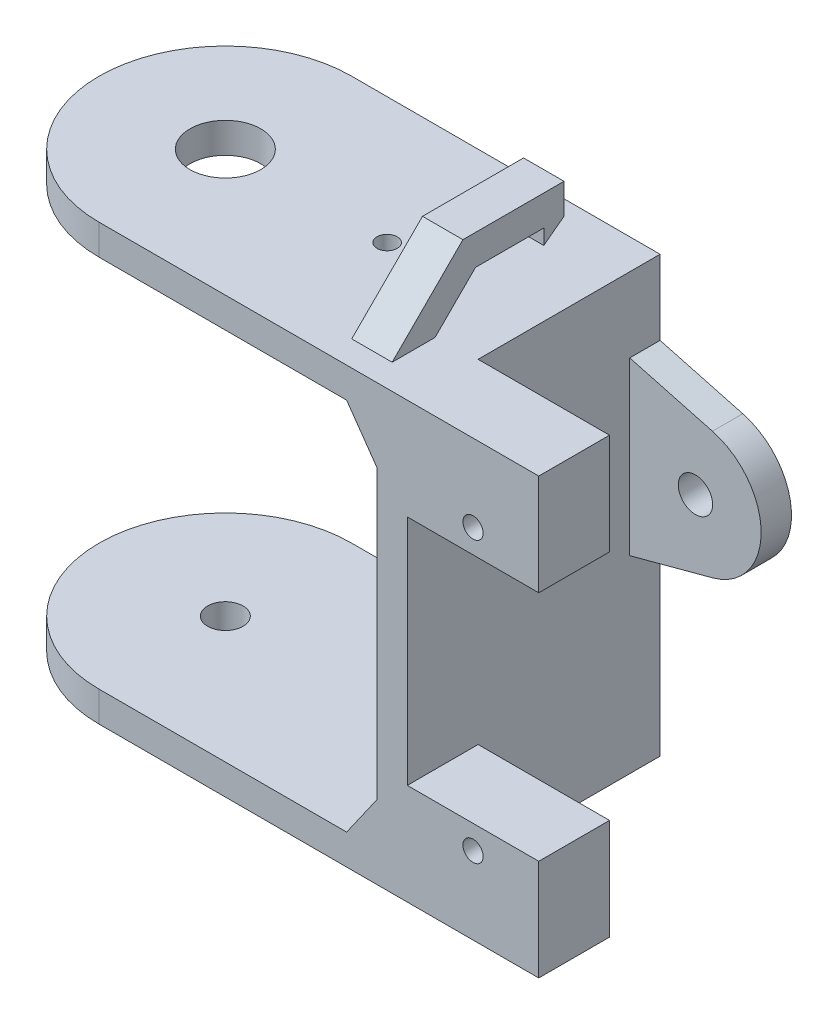
SolidWorks part; units mm, degrees
ref_plane "Plano frontal" through (0, 0, 0) normal (0, 0, 1) x (1, 0, 0)
ref_plane "Plano superior" through (0, 0, 0) normal (0, 1, 0) x (1, 0, 0)
ref_plane "Plano direito" through (0, 0, 0) normal (1, 0, 0) x (0, 0, -1)
sketch "Esboço1" plane through (0, 0, 0) normal (0, 0, 1) x (1, 0, 0)
  line L1 (0, -21.5) -> (-43, -21.5)
  line L2 (-43, -21.5) -> (-43, -18.5)
  line L3 (-43, -18.5) -> (-3, -18.5)
  line L4 (-3, -18.5) -> (-3, 18.5)
  line L5 (-3, 18.5) -> (-43, 18.5)
  line L6 (-43, 18.5) -> (-43, 21.5)
  line L7 (-43, 21.5) -> (0, 21.5)
  line L8 (0, 21.5) -> (13, 21.5)
  line L9 (13, 21.5) -> (13, 11.5)
  line L10 (13, 11.5) -> (0, 11.5)
  line L11 (0, -21.5) -> (13, -21.5)
  line L12 (13, -21.5) -> (13, -11.5)
  line L13 (13, -11.5) -> (0, -11.5)
  line L14 (0, 11.5) -> (0, -11.5)
  line L17 (0, 0) -> (31.9596, 0) construction
  circle A0 centre (6.5, 13.85) radius 1
  circle A2 centre (6.5, -13.85) radius 1
  point P4 (0, 0)
  point P7 (0, 0)
  point P12 (-7, 23)
  point P16 (0, 0)
  point P19 (0, 0)
  point P20 (-3, 0)
  point P23 (6.5, 11.5)
  point P24 (0, 0)
  point P30 (6.5, -24.315)
  point P31 (0, 21.5)
  point P32 (0, 21.5)
  point P33 (0, -21.5)
  dimension "D9" = 2
  dimension "D1" = 23
  dimension "D2" = 3
  dimension "D3" = 13
  dimension "D5" = 3
  dimension "D6" = 37
  dimension "D7" = 40
  dimension "D10" = 27.7
extrude "Ressalto-extrusão1" add sketch "Esboço1" along normal mid plane 25
sketch "Esboço2" plane through (0, 21.5, 0) normal (0, 1, 0) x (1, 0, 0)
  line L0 (-30.5, 12.5) -> (-64.1593, 12.5)
  line L1 (-64.1593, 12.5) -> (-64.1593, -12.5)
  line L2 (0, 0) -> (-3.8141, 0) construction
  line L3 (-64.1593, -12.5) -> (-30.5, -12.5)
  line L4 (-43, -12.5) -> (-43, 12.5) construction
  line L5 (13, 12.5) -> (-43, 12.5) construction
  circle A0 centre (-30.5, 0) radius 3.5
  circle A1 centre (-14.5, 0) radius 1
  arc A7 (-30.5, 12.5) -> (-30.5, -12.5) centre (-30.5, 0) ccw
  point P4 (-21.75, 0)
  point P5 (-59.3343, 15.2284)
  point P9 (-3.8141, 0)
  point P10 (-10.9, 0)
  point P13 (0, 0)
  point P19 (-35, 0)
  point P25 (-57.8021, 17.5)
  point P26 (-64.9885, 25.6125)
  point P27 (-73.7699, 34.1272)
  point P28 (-63.3875, 22.5081)
  point P29 (-64.9885, 24.6125)
  line M3 (13, 12.5) -> (-43, 12.5)
  line M4 (-43, 12.5) -> (-43, -12.5)
  line M5 (-43, -12.5) -> (13, -12.5)
  dimension "D1" = 7
  dimension "D3" = 2
  dimension "D2" = 16
extrude "Corte-extrusão1" cut sketch "Esboço2" against normal blind 15
sketch "Esboço4" plane through (0, -11.5, 0) normal (0, 1, 0) x (1, 0, 0)
  line L0 (13, -12.5) -> (13, 12.5) construction
  line L1 (13, -5.5) -> (0, -5.5)
  line L2 (13, -5.5) -> (13, 12.5)
  line L3 (13, 12.5) -> (0, 12.5)
  line L4 (0, -5.5) -> (0, 12.5)
  line L5 (13, -12.5) -> (0, -12.5) construction
  dimension "D1" = 7
extrude "Corte-extrusão2" cut sketch "Esboço4" against normal through all both and the other way through all
sketch "Esboço5" plane through (0, 0, -12.5) normal (0, 0, -1) x (-1, 0, 0)
  line L0 (-6.5, 13.85) -> (-6.5, -13.85) construction
  line L1 (-8.1823, 11.9285) -> (0, 14.121)
  line L2 (0, -11.5) -> (0, 11.5) construction
  line L3 (-8.1823, -0.6285) -> (0, -2.821)
  line L4 (0, 14.121) -> (0, -2.821)
  line L7 (-13, 11.5) -> (-13, 21.5) construction
  arc A0 (-8.1823, 11.9285) -> (-8.1823, -0.6285) centre (-6.5, 5.65) ccw
  circle A1 centre (-6.5, 5.65) radius 1.7
  point P1 (0, 0)
  point P6 (-6.5, 6.0782)
  point P8 (0, 15.1492)
  point P15 (0, 0)
  point P16 (-6.5, 0)
  dimension "D1" = 3.4
  dimension "D3" = 5.65
  dimension "D2" = 75
extrude "Ressalto-extrusão2" add sketch "Esboço5" against normal blind 3
chamfer "Chanfro1" distance 3 angle 55 2 edges at (-3, -18.5, 0) (-3, 18.5, 0) first distance on face at (-23, -18.5, 0) first distance on face at (-15.5, 18.5, 0)
sketch "Esboço7" plane through (0, -18.5, 0) normal (0, 1, 0) x (1, 0, 0)
  circle A0 centre (-30.5, 0) radius 1.75
  dimension "D1" = 3.5
extrude "Corte-extrusão3" cut sketch "Esboço7" against normal blind 10
extrude "Corte-extrusão4" cut sketch "Esboço2<2>" against normal through all contours L1 L3 L0 M4 | A7 M4 M5 | A7 M3 M4 region at (-40.2079, 21.5, -9.7079) region at (-53.5796, 21.5, 0) region at (-40.2079, 21.5, 9.7079)
sketch "Esboço2<2>" plane through (0, 21.5, 0) normal (0, 1, 0) x (1, 0, 0) same geometry as "Esboço2"
sketch "Esboço8" plane through (0, 0, 0) normal (1, 0, 0) x (0, 0, -1)
  line L0 (-10, 21.5) -> (-3, 28.5)
  line L1 (-12.5, 21.5) -> (-5.5, 21.5) construction
  line L2 (-3, 28.5) -> (7, 28.5)
  line L3 (7, 28.5) -> (7, 25.5)
  line L4 (7, 25.5) -> (5, 24)
  line L5 (5, 24) -> (5, 25.5)
  line L6 (5, 25.5) -> (-1.7574, 25.5)
  line L7 (-1.7574, 25.5) -> (-5.7574, 21.5)
  line L8 (-5.7574, 21.5) -> (-10, 21.5)
  line L9 (1.6213, 28.5) -> (1.6213, 25.5) construction
  line L13 (-1.7574, 25.5) -> (-3.8787, 27.6213) construction
  point P14 (1.6213, 25.5)
  dimension "D1" = 4
  dimension "D2" = 3
  dimension "D3" = 3
  dimension "D4" = 1.5
  dimension "D5" = 2
  dimension "D6" = 10
  dimension "D7" = 45
  dimension "D8" = 2.5
extrude "Ressalto-extrusão3" add sketch "Esboço8" against normal blind 4 from offset 4 offset against normal yes
sketch "Esboço9" plane through (0, -18.5, 0) normal (0, 1, 0) x (1, 0, 0)
  line L0 (-6, 12.5) -> (-30.5, 12.5) construction
  line L1 (-6, -12.5) -> (-30.5, -12.5) construction
  line L2 (-5.4451, 12.5) -> (-5.4451, -12.5)
  arc A0 (-5.4451, 12.5) -> (-5.4451, -12.5) centre (-30.5, 0) cw
  dimension "D1" = 28
